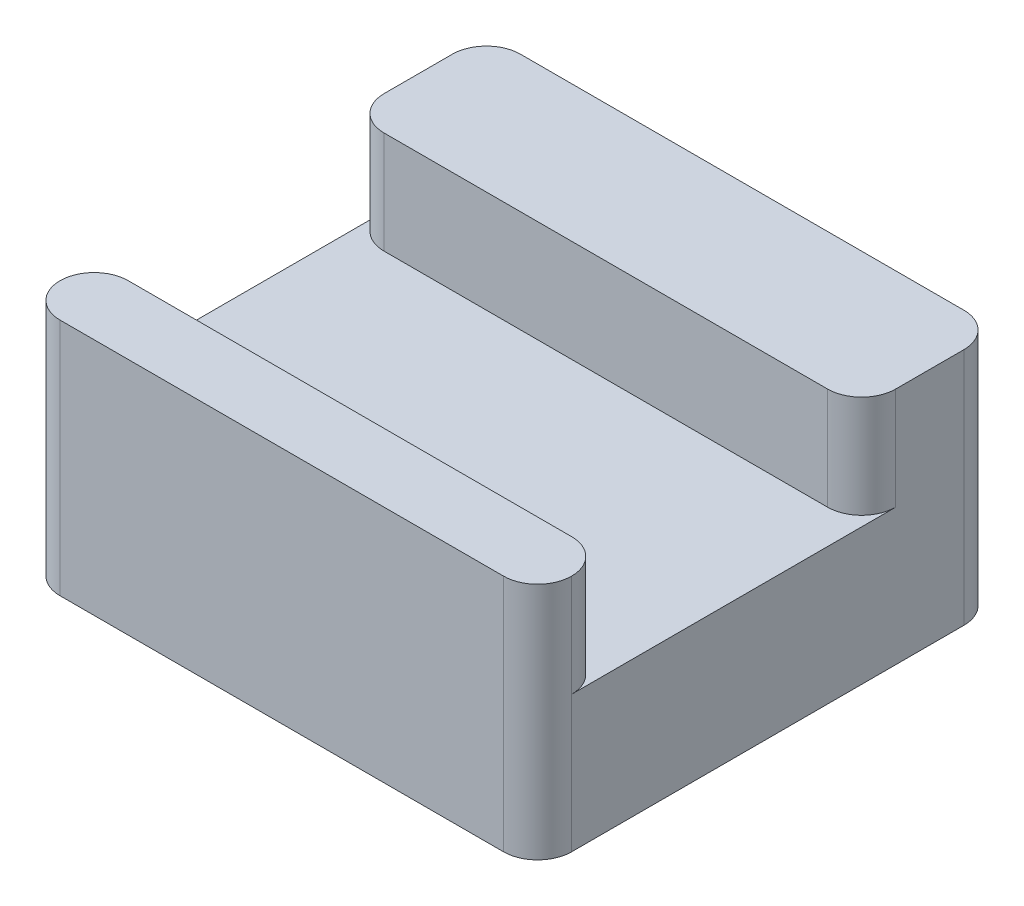
SolidWorks part; units mm, degrees
ref_plane "Front Plane" through (0, 0, 0) normal (0, 0, 1) x (1, 0, 0)
ref_plane "Top Plane" through (0, 0, 0) normal (0, 1, 0) x (1, 0, 0)
ref_plane "Right Plane" through (0, 0, 0) normal (1, 0, 0) x (0, 0, -1)
sketch "Sketch1" plane through (0, 0, 0) normal (0, 1, 0) x (1, 0, 0)
  line L1 (-7.5, -6.75) -> (7.5, -6.75)
  line L2 (-7.5, -6.75) -> (-7.5, 6.75)
  line L3 (-7.5, 6.75) -> (7.5, 6.75)
  line L4 (7.5, -6.75) -> (7.5, 6.75)
  line L5 (-7.5, -6.75) -> (7.5, 6.75) construction
  line L6 (-7.5, 6.75) -> (7.5, -6.75) construction
  point P0 (0, 0)
  dimension "D1" = 15
  dimension "D2" = 13.5
extrude "Boss-Extrude1" add sketch "Sketch1" along normal blind 7
sketch "Sketch2" plane through (0, 7, 0) normal (0, 1, 0) x (1, 0, 0)
  line L0 (-7.5, -6.75) -> (7.5, -6.75) construction
  line L1 (-7.5, -4.75) -> (7.5, -4.75)
  line L2 (-7.5, -4.75) -> (-7.5, 2.75)
  line L3 (-7.5, 2.75) -> (7.5, 2.75)
  line L4 (7.5, -4.75) -> (7.5, 2.75)
  line L5 (-7.5, -4.75) -> (7.5, 2.75) construction
  line L6 (-7.5, 2.75) -> (7.5, -4.75) construction
  line L7 (-7.5, 6.75) -> (-7.5, -6.75) construction
  line L8 (7.5, -6.75) -> (7.5, 6.75) construction
  point P0 (0, -1)
  dimension "D1" = 2
  dimension "D2" = 7.5
extrude "Cut-Extrude2" cut sketch "Sketch2" against normal blind 3
sketch "Sketch3" plane through (0, 0, -6.75) normal (0, 0, -1) x (-1, 0, 0)
  line L0 (-7.5, 0) -> (7.5, 0) construction
  line L1 (0, 3.85) -> (0, -3.85) construction
  circle A0 centre (0, 2) radius 1.3
  dimension "D1" = 2.6
  dimension "D2" = 2
extrude "Cut-Extrude3" cut sketch "Sketch3" against normal blind 10.5
fillet "Fillet1" radius 1 8 edges at (-7.5, 3.5, 6.75) (-7.5, 5.5, 4.75) (-7.5, 5.5, -2.75) (-7.5, 3.5, -6.75) (7.5, 3.5, -6.75) (7.5, 5.5, -2.75) (7.5, 5.5, 4.75) (7.5, 3.5, 6.75)
